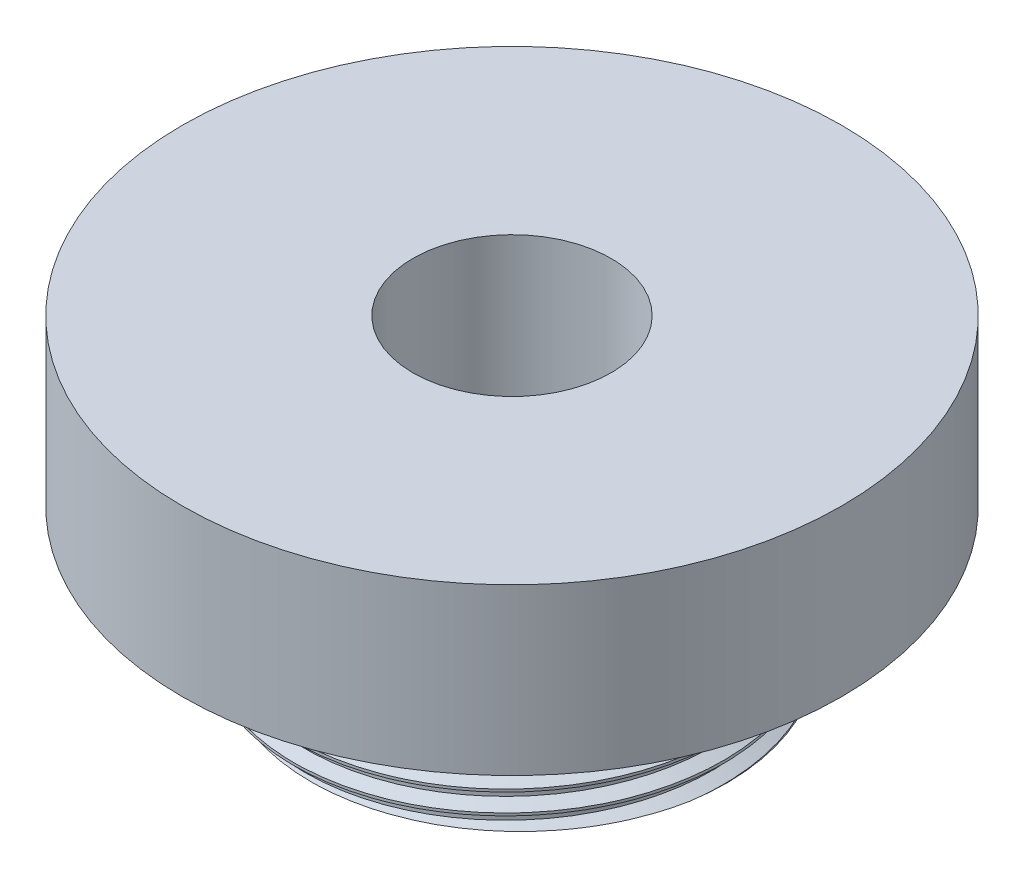
SolidWorks part; units mm, degrees
material "PE High Density"
ref_plane "Front Plane" through (0, 0, 0) normal (0, 0, 1) x (1, 0, 0)
ref_plane "Top Plane" through (0, 0, 0) normal (0, 1, 0) x (1, 0, 0)
ref_plane "Right Plane" through (0, 0, 0) normal (1, 0, 0) x (0, 0, -1)
sketch "Sketch1" plane through (0, 0, 0) normal (0, 1, 0) x (1, 0, 0)
  circle A0 centre (0, 0) radius 16.51
extrude "Boss-Extrude1" add sketch "Sketch1" along normal blind 10.16
thread "Thread1" pitch 1.5875 method cut profile "Thread Profile1" start angle 0, offset 0, length 10, pitch 1.5875, diameter 33.02
ref_plane "Plane1" through (-16.51, 10.16, 0) normal (0, 0, 1) x (-1, 0, 0)
sketch "Thread Profile1" plane through (-16.51, 10.16, 0) normal (0, 0, 1) x (-1, 0, 0)
  line L0 (0, 0) -> (0, 1.5875) construction
  line L11 (0, 0) -> (0, 1.3891)
  line L12 (0, 1.3891) -> (-0.8593, 0.893)
  line L13 (-0.8593, 0.893) -> (-0.8593, 0.4961)
  line L15 (-0.8593, 0.4961) -> (0, 0)
  line L17 (-0.8593, 0.6945) -> (0, 0.6945) construction
  point P2 (0, 0)
  dimension "Pitch" = 1.5875
  dimension "Profile_Angle" = 60
  dimension "Profile_Land" = 0.3969
  dimension "Profile_Height" = 0.8593
sketch "Sketch4" plane through (0, 10.16, 0) normal (0, 1, 0) x (1, 0, 0)
  circle A0 centre (0, 0) radius 25.3412
extrude "Boss-Extrude2" add sketch "Sketch4" along normal blind 12.7
sketch "Sketch5" plane through (0, 22.86, 0) normal (0, 1, 0) x (1, 0, 0)
  circle A0 centre (0, 0) radius 7.62
extrude "Cut-Extrude1" cut sketch "Sketch5" against normal blind 25.4
